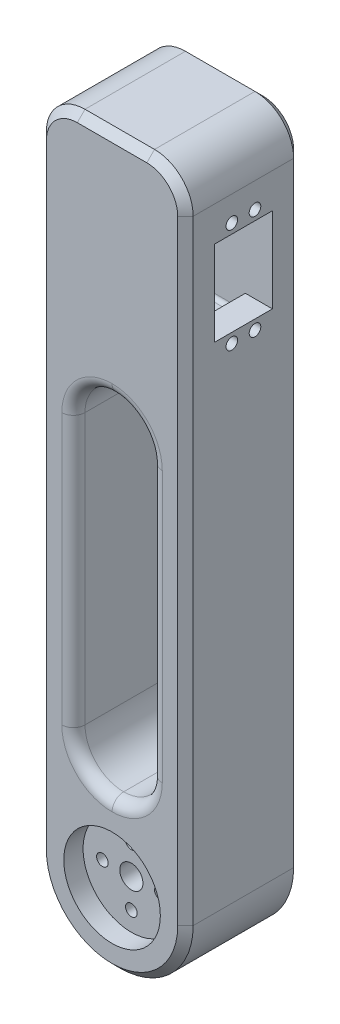
SolidWorks part; units mm, degrees
ref_plane "Front Plane" through (0, 0, 0) normal (0, 0, 1) x (1, 0, 0)
ref_plane "Top Plane" through (0, 0, 0) normal (0, 1, 0) x (1, 0, 0)
ref_plane "Right Plane" through (0, 0, 0) normal (1, 0, 0) x (0, 0, -1)
sketch "Sketch1" plane through (0, 0, 0) normal (0, 0, 1) x (1, 0, 0)
  line L0 (0, 0) -> (0, 150) construction
  line L1 (19, 150) -> (19, 0)
  line L2 (-19, 150) -> (-19, 0)
  line L5 (19, 150) -> (19, 169)
  line L6 (19, 169) -> (-19, 169)
  line L7 (-19, 150) -> (-19, 169)
  arc A1 (-19, 0) -> (19, 0) centre (0, 0) ccw
  dimension "D2" = 38
  dimension "D3" = 38
  dimension "D1" = 169
extrude "Boss-Extrude1" add sketch "Sketch1" along normal blind 30
sketch "Sketch2" plane through (0, 0, 30) normal (0, 0, 1) x (1, 0, 0)
  line L0 (0, 0) -> (0, 10.7915) construction
  line L1 (0, 0) -> (0, -10.5073) construction
  circle A0 centre (0, 0) radius 12.5
  circle A1 centre (0, 0) radius 3
  circle A2 centre (0, 7.5) radius 1.5
  circle A3 centre (7.5, 0) radius 1.5
  circle A4 centre (0, -7.5) radius 1.5
  circle A5 centre (-7.5, 0) radius 1.5
  point P16 (0, 0)
  dimension "D1" = 25
  dimension "D2" = 3
  dimension "D3" = 6
  dimension "D4" = 7.5
  dimension "D6" = 7.5
  dimension "D5" = 4
extrude "Cut-Extrude1" cut sketch "Sketch2" against normal blind 5 contours A0
sketch "Sketch3" plane through (0, 0, 25) normal (0, 0, 1) x (1, 0, 0)
  line L0 (0, 11.9636) -> (0, -10.8812) construction
  line L1 (0, 0) -> (10.7896, 0) construction
  circle A0 centre (0, 0) radius 3
  circle A1 centre (0, 7.5) radius 1.5
  circle A2 centre (7.5, 0) radius 1.5
  circle A3 centre (0, -7.5) radius 1.5
  circle A4 centre (-7.5, 0) radius 1.5
  point P16 (0, 0)
  dimension "D1" = 6
  dimension "D2" = 3
  dimension "D3" = 7.5
  dimension "D4" = 4
extrude "Cut-Extrude3" cut sketch "Sketch3" against normal blind 10
sketch "Sketch5" plane through (-19, 0, 0) normal (-1, 0, 0) x (0, 0, 1)
  line L0 (15, 169) -> (15, -19) construction
  line L1 (30, 169) -> (0, 169) construction
  line L2 (0, -19) -> (30, -19) construction
  line L4 (7.5, 155) -> (22.5, 155)
  line L5 (7.5, 155) -> (7.5, 123)
  line L6 (7.5, 123) -> (22.5, 123)
  line L7 (22.5, 155) -> (22.5, 123)
  line L8 (7.5, 155) -> (22.5, 123) construction
  line L9 (7.5, 123) -> (22.5, 155) construction
  point P6 (15, 139)
  dimension "D1" = 32
  dimension "D2" = 15
  dimension "D3" = 30
extrude "Cut-Extrude4" cut sketch "Sketch5" against normal blind 31
sketch "Sketch6" plane through (12, 0, 0) normal (-1, 0, 0) x (0, 0, 1)
  line L0 (15, 155) -> (15, 123) construction
  line L1 (22.5, 155) -> (7.5, 155) construction
  line L2 (7.5, 123) -> (22.5, 123) construction
  line L3 (7.5, 155) -> (7.5, 123) construction
  line L4 (7.5, 150) -> (22.5, 150)
  line L5 (7.5, 150) -> (7.5, 128)
  line L6 (7.5, 128) -> (22.5, 128)
  line L7 (22.5, 150) -> (22.5, 128)
  line L8 (22.5, 123) -> (22.5, 155) construction
  line L9 (22.5, 155) -> (7.5, 155) construction
  line L10 (7.5, 123) -> (22.5, 123) construction
  line L11 (7.5, 152.5) -> (22.5, 152.5) construction
  line L12 (7.5, 155) -> (7.5, 123) construction
  line L13 (22.5, 123) -> (22.5, 155) construction
  line L15 (7.5, 139) -> (22.5, 139) construction
  circle A0 centre (12, 152.5) radius 1.5
  circle A2 centre (18, 152.5) radius 1.5
  circle A3 centre (18, 125.5) radius 1.5
  circle A4 centre (12, 125.5) radius 1.5
  dimension "D4" = 3
  dimension "D1" = 5
  dimension "D2" = 5
  dimension "D3" = 2.5
  dimension "D6" = 3
extrude "Cut-Extrude5" cut sketch "Sketch6" against normal through all
fillet "Fillet2" radius 10 2 edges at (19, 169, 15) (-19, 169, 15)
chamfer "Chamfer2" distance 2 12 edges at (0, 169, 0) (-16.0711, 166.0711, 0) (16.0711, 166.0711, 0) (19, 79.5, 0) (0, -19, 0) (-19, 79.5, 0) (0, -19, 30) (19, 79.5, 30) (16.0711, 166.0711, 30) (0, 169, 30) (-16.0711, 166.0711, 30) (-19, 79.5, 30)
sketch "Sketch7" plane through (0, 0, 0) normal (0, 0, -1) x (-1, 0, 0)
  line L0 (-10, 159) -> (-10, 0) construction
  line L1 (0, 169) -> (0, -19) construction
  line L2 (-9, 169) -> (9, 169) construction
  line L3 (10, 159) -> (10, 0) construction
  line L5 (-10, 110) -> (10, 110)
  line L6 (-10, 110) -> (-10, 20)
  line L7 (-10, 20) -> (10, 20)
  line L8 (10, 110) -> (10, 20)
  arc A0 (-19, 0) -> (19, 0) centre (0, 0) ccw construction
  dimension "D1" = 10
  dimension "D2" = 90
  dimension "D3" = 20
extrude "Cut-Extrude6" cut sketch "Sketch7" against normal through all
fillet "Fillet3" radius 10 4 edges at (-10, 110, 15) (10, 20, 15) (-10, 20, 15) (10, 110, 15)
fillet "Fillet4" radius 1 4 edges at (-3.5, 155, 22.5) (-3.5, 155, 7.5) (-3.5, 123, 7.5) (-3.5, 123, 22.5)
fillet "Fillet5" radius 3 12 edges at (7.0711, 107.0711, 0) (-7.0711, 107.0711, 0) (-10, 65, 0) (-7.0711, 22.9289, 0) (7.0711, 22.9289, 0) (7.0711, 107.0711, 30) (-7.0711, 107.0711, 30) (-10, 65, 30) (-7.0711, 22.9289, 30) (7.0711, 22.9289, 30) (10, 65, 0) (10, 65, 30)
